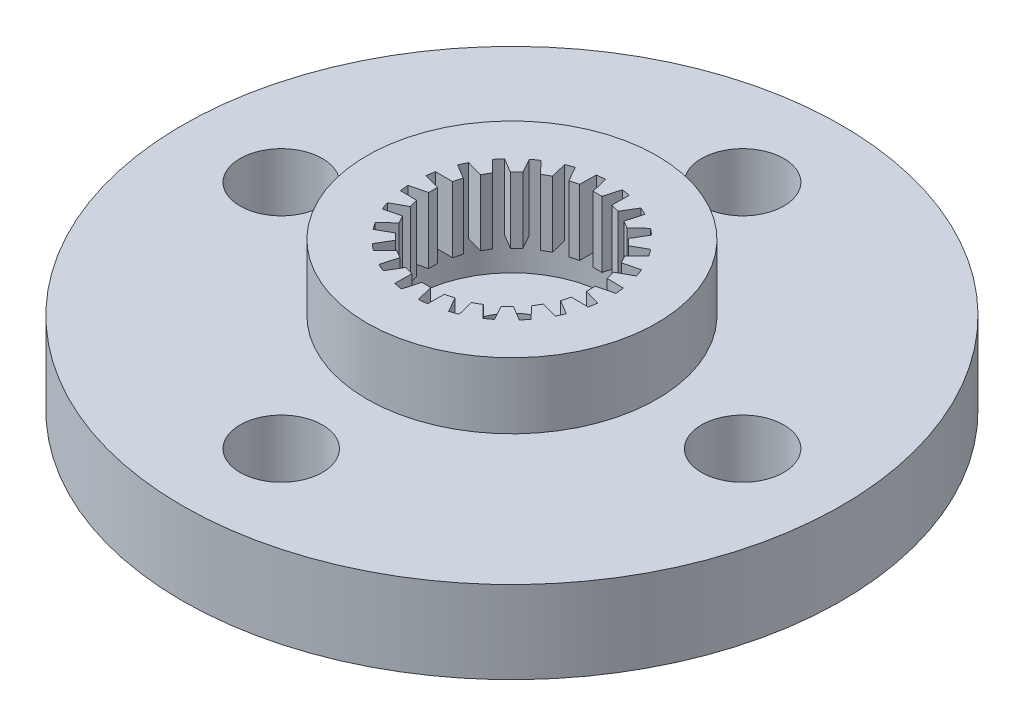
SolidWorks part; units mm, degrees
material "AISI 304"
ref_plane "前视基准面" through (0, 0, 0) normal (0, 0, 1) x (1, 0, 0)
ref_plane "上视基准面" through (0, 0, 0) normal (0, 1, 0) x (1, 0, 0)
ref_plane "右视基准面" through (0, 0, 0) normal (1, 0, 0) x (0, 0, -1)
sketch "草图4" plane through (0, 0, 0) normal (0, 1, 0) x (1, 0, 0)
  circle A0 centre (0, 0) radius 10
  dimension "D1" = 20
extrude "凸台-拉伸2" add sketch "草图4" along normal blind 2.5
ref_plane "基准面7" through (0, 2.5, 0) normal (0, 1, 0) x (1, 0, 0)
sketch "草图7" plane through (0, 2.5, 0) normal (0, 1, 0) x (1, 0, 0)
  circle A0 centre (0, 0) radius 4.4
  dimension "D1" = 8.8
extrude "凸台-拉伸3" add sketch "草图7" along normal blind 2
ref_plane "基准面8" through (0, 4.5, 0) normal (0, 1, 0) x (1, 0, 0)
sketch "草图8" plane through (0, 4.5, 0) normal (0, 1, 0) x (1, 0, 0)
  circle A0 centre (0, 0) radius 3
  dimension "D1" = 6
extrude "切除-拉伸10" cut sketch "草图8" against normal blind 3
ref_axis "基准轴1" through (0, 1.5, 0) along (0, 1, 0)
sketch "草图14" plane through (0, 4.5, 0) normal (0, 1, 0) x (1, 0, 0)
  line L0 (2.9769, -0.3715) -> (2.4958, -0.2354)
  line L1 (2.4958, -0.2354) -> (2.4958, 0.0323)
  line L2 (2.4958, 0.0323) -> (2.9958, 0.1588)
  arc A0 (2.9769, -0.3715) -> (2.9958, 0.1588) centre (0, 0) ccw
  dimension "D3" = 3
  dimension "D1" = 30
  dimension "D2" = 0.5
  dimension "0.5" = 0.5
extrude "凸台-拉伸5" add sketch "草图14" against normal blind 2
pattern_circular "阵列(圆周)1" count 24 every 15 about axis through (0, 4.5, 0) along (0, 1, 0) of "凸台-拉伸5"
hole_wizard "M3 螺纹孔1" positions "草图17" profile "草图16" tap size "M3" standard "GB" end condition through all
sketch "草图17" plane through (0, 0, 0) normal (0, -1, 0) x (-1, 0, 0)
  circle A0 centre (0, 0) radius 7 construction
  point P0 (0, -7)
  point P2 (7, 0)
  point P4 (0, 7)
  point P6 (-7, 0)
  dimension "D1" = 14
sketch "草图16" plane through (0, 0, 7) normal (1, 0, 0) x (0, 0, -1)
  line L0 (0, 0) -> (0, 4.5)
  line L1 (0, 4.5) -> (1.25, 4.5)
  line L2 (1.25, 4.5) -> (1.25, 0)
  line L5 (1.25, 0) -> (0, 0)
  line L11 (0, -6.35) -> (0, 107.95) construction
  dimension "通孔螺纹孔钻头直径" = 2.5
  dimension "通孔螺纹孔钻头深度" = 4.5
cosmetic thread "孔螺蚊线1" parameters "D2"=3
cosmetic thread "孔螺蚊线2" parameters "D2"=3
cosmetic thread "孔螺蚊线3" parameters "D2"=3
cosmetic thread "孔螺蚊线4" parameters "D2"=3
sketch "草图18" plane through (0, 0, 0) normal (0, -1, 0) x (1, 0, 0)
  circle A0 centre (0, 0) radius 1.5
  dimension "D1" = 3
extrude "切除-拉伸11" cut sketch "草图18" against normal up to next
sketch "草图19" plane through (0, 0, 0) normal (0, -1, 0) x (1, 0, 0)
  circle A0 centre (0, 7) radius 1.25
